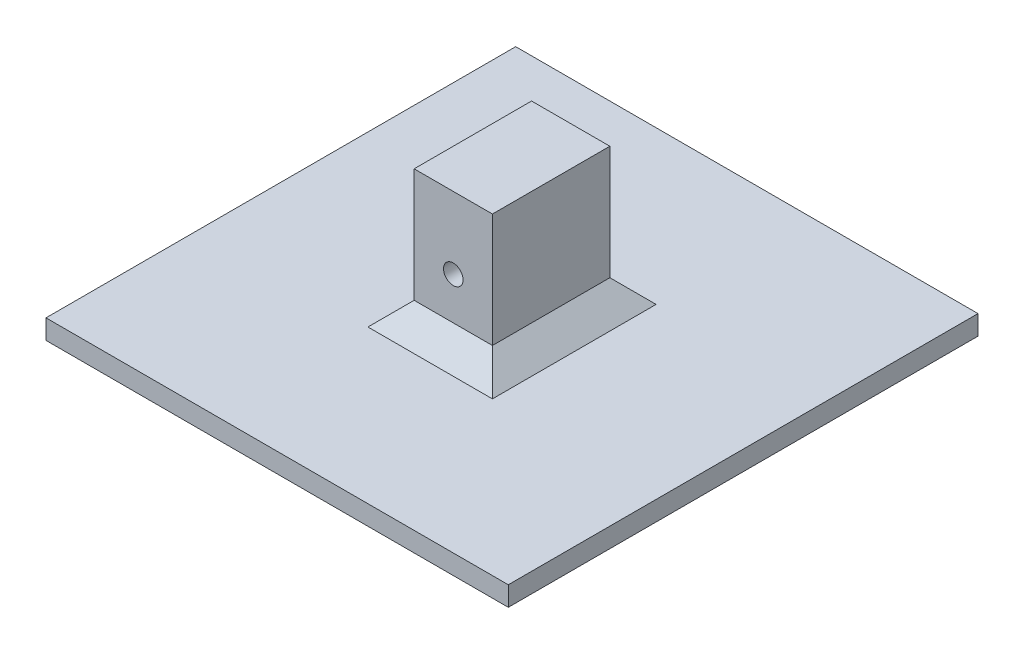
SolidWorks part; units mm, degrees
ref_plane "Front Plane" through (0, 0, 0) normal (0, 0, 1) x (1, 0, 0)
ref_plane "Top Plane" through (0, 0, 0) normal (0, 1, 0) x (1, 0, 0)
ref_plane "Right Plane" through (0, 0, 0) normal (1, 0, 0) x (0, 0, -1)
sketch "Sketch-Profile" plane through (0, 0, 0) normal (1, 0, 0) x (0, 0, -1)
  line L0 (-76.2, 6.35) -> (-76.2, 0)
  line L5 (-76.2, 6.35) -> (-19.05, 6.35)
  line L6 (-76.2, 0) -> (76.2, 0)
  line L7 (76.2, 6.35) -> (76.2, 0)
  line L8 (-76.2, 6.35) -> (76.2, 0) construction
  line L9 (-76.2, 0) -> (76.2, 6.35) construction
  line L10 (-19.05, 50.8) -> (-19.05, 6.35)
  line L11 (-19.05, 50.8) -> (19.05, 50.8)
  line L13 (19.05, 50.8) -> (19.05, 6.35)
  line L14 (-19.05, 50.8) -> (19.05, 6.35) construction
  line L15 (-19.05, 6.35) -> (19.05, 50.8) construction
  line L16 (19.05, 6.35) -> (76.2, 6.35)
  point P1 (0, 3.175)
  point P2 (0, 28.575)
  dimension "D1" = 6.35
  dimension "D2" = 50.8
  dimension "D3" = 152.4
  dimension "D4" = 38.1
extrude "Boss-Extrude1" add sketch "Sketch-Profile" along normal blind 12.7 and the other way blind 12.7
sketch "Sketch-Hole Location" plane through (0, 0, 19.05) normal (0, 0, 1) x (1, 0, 0)
  line L0 (0, 0) -> (0, 50.8) construction
  line L1 (12.7, 0) -> (-12.7, 0) construction
  line L2 (12.7, 50.8) -> (-12.7, 50.8) construction
  line L3 (109.3309, 27.5181) -> (22.8959, 27.5181) construction
  point P6 (0, 27.5181)
sketch "Sketch5" plane through (0, 0, 19.05) normal (0, 0, 1) x (1, 0, 0)
  point P0 (0, 27.5181)
hole_wizard "1/4 (0.25) Diameter Hole1" positions "Sketch5" profile "Sketch4" hole size "1/4" standard "ANSI Inch" end condition through all
sketch "Sketch4" plane through (0, 27.5181, 19.05) normal (1, 0, 0) x (0, -1, 0)
  line L0 (0, 0) -> (0, 95.25)
  line L1 (0, 95.25) -> (3.175, 95.25)
  line L2 (3.175, 95.25) -> (3.175, 0)
  line L5 (3.175, 0) -> (0, 0)
  line L11 (0, -6.35) -> (0, 107.95) construction
  dimension "Thru Hole Dia." = 6.35
  dimension "Thru Hole Depth" = 95.25
sketch "Sketch6" plane through (0, 0, 0) normal (1, 0, 0) x (0, 0, -1)
  line L0 (76.2, 0) -> (76.2, 6.35) construction
  line L1 (-76.2, 0) -> (76.2, 0) construction
  line L2 (-76.2, 6.35) -> (-76.2, 0) construction
  line L3 (76.2, 0) -> (76.2, 6.35)
  line L4 (-76.2, 0) -> (76.2, 0)
  line L5 (-76.2, 6.35) -> (-76.2, 0)
  line L6 (-76.2, 6.35) -> (76.2, 6.35)
extrude "Boss-Extrude2" add sketch "Sketch6" along normal blind 75 and the other way blind 75
chamfer "Chamfer1" distance 7.5 angle 45 4 edges at (0, 6.35, 19.05) (-12.7, 6.35, 0) (0, 6.35, -19.05) (12.7, 6.35, 0)
